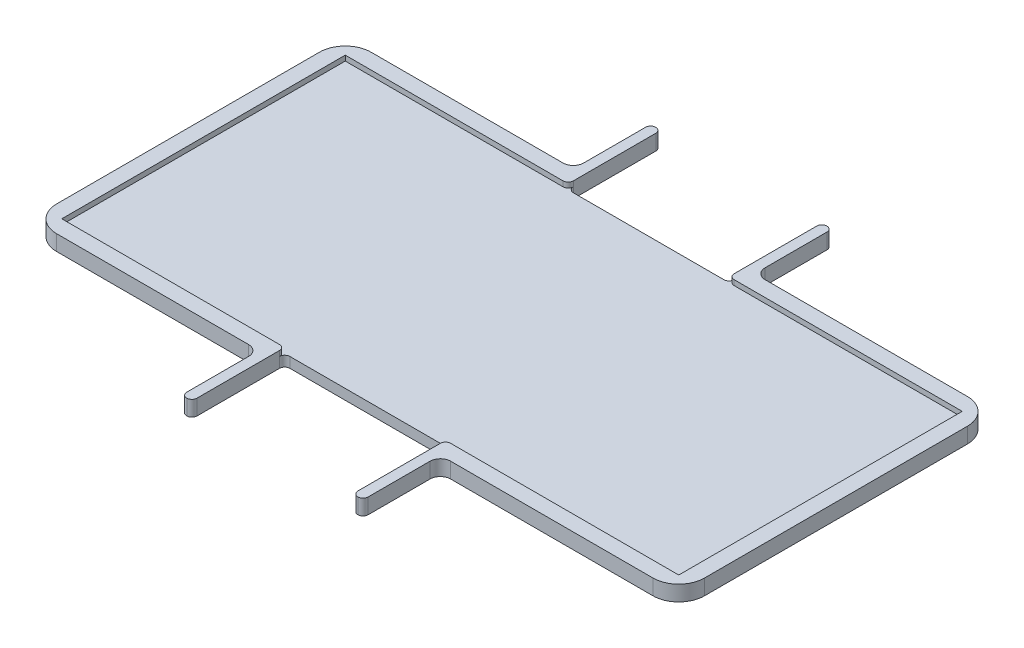
SolidWorks part; units mm, degrees
ref_plane "Front Plane" through (0, 0, 0) normal (0, 0, 1) x (1, 0, 0)
ref_plane "Top Plane" through (0, 0, 0) normal (0, 1, 0) x (1, 0, 0)
ref_plane "Right Plane" through (0, 0, 0) normal (1, 0, 0) x (0, 0, -1)
sketch "Sketch1" plane through (0, 0, 0) normal (0, 1, 0) x (1, 0, 0)
  line L0 (-3, -3) -> (41.25, -3)
  line L1 (0, 0) -> (119.7, 0)
  line L2 (0, 0) -> (0, 55)
  line L3 (0, 55) -> (119.7, 55)
  line L4 (119.7, 0) -> (119.7, 55)
  line L5 (122.7, -3) -> (122.7, 58)
  line L6 (-3, 58) -> (41.25, 58)
  line L7 (-3, -3) -> (-3, 58)
  line L8 (58.85, 55) -> (58.85, 0) construction
  line L9 (0, 27.5) -> (119.7, 27.5) construction
  line L10 (74.45, 58) -> (74.45, 73)
  line L12 (41.25, 58) -> (41.25, 73)
  line L13 (41.25, 73) -> (43.25, 73)
  line L14 (43.25, 58) -> (43.25, 73)
  line L15 (76.45, 73) -> (74.45, 73)
  line L16 (76.45, 58) -> (76.45, 73)
  line L19 (76.45, -3) -> (76.45, -18)
  line L20 (76.45, -18) -> (74.45, -18)
  line L21 (43.25, -3) -> (43.25, -18)
  line L22 (41.25, -18) -> (43.25, -18)
  line L23 (41.25, -3) -> (41.25, -18)
  line L25 (74.45, -3) -> (74.45, -18)
  line L27 (-3, -3) -> (122.7, -3) construction
  line L28 (76.45, -3) -> (122.7, -3)
  line L30 (-3, 58) -> (122.7, 58) construction
  line L31 (76.45, 58) -> (122.7, 58)
  line L32 (43.25, 58) -> (43.25, 55)
  line L33 (43.25, 55) -> (74.45, 55)
  line L34 (74.45, 55) -> (74.45, 58)
  line L35 (43.25, -3) -> (43.25, 0)
  line L36 (43.25, 0) -> (74.45, 0)
  line L37 (74.45, 0) -> (74.45, -3)
  dimension "D1" = 119.7
  dimension "D2" = 3
  dimension "54.8" = 55
  dimension "D3" = 15.6
  dimension "D4" = 2
  dimension "D5" = 15
extrude "Boss-Extrude3" add sketch "Sketch1" along normal blind 3 contours L1 L37 L25 L20 L19 L28 L5 L31 L16 L15 L10 L34 L3 L4 | L21 L35 L1 L2 L3 L32 L14 L13 L12 L6 L7 L0 L23 L22 region at (-1.9792, 0, -27.5) region at (97.075, 0, 1.03)
sketch "Sketch2" plane through (0, 0, 0) normal (0, 1, 0) x (1, 0, 0)
  line L6 (0, 55) -> (119.7, 55)
  line L7 (0, 55) -> (0, 0)
  line L8 (0, 0) -> (119.7, 0)
  line L9 (119.7, 55) -> (119.7, 0)
extrude "Boss-Extrude4" add sketch "Sketch2" along normal blind 2
fillet "Fillet5" radius 2 4 edges at (76.45, 1.5, -58) (41.25, 1.5, -58) (41.25, 1.5, 3) (76.45, 1.5, 3)
fillet "Fillet6" radius 5 4 edges at (122.7, 1.5, 3) (122.7, 1.5, -58) (-3, 1.5, 3) (-3, 1.5, -58)
fillet "Fillet7" radius 1 8 edges at (74.45, 1.5, 18) (76.45, 1.5, 18) (43.25, 1.5, 18) (41.25, 1.5, 18) (41.25, 1.5, -73) (43.25, 1.5, -73) (74.45, 1.5, -73) (76.45, 1.5, -73)
fillet "Fillet8" radius 1 4 edges at (74.45, 2.5, 0) (43.25, 2.5, 0) (74.45, 2.5, -55) (43.25, 2.5, -55)
fillet "Fillet9" radius 1 4 edges at (43.25, 1, -55) (74.45, 1, -55) (74.45, 1, 0) (43.25, 1, 0)
